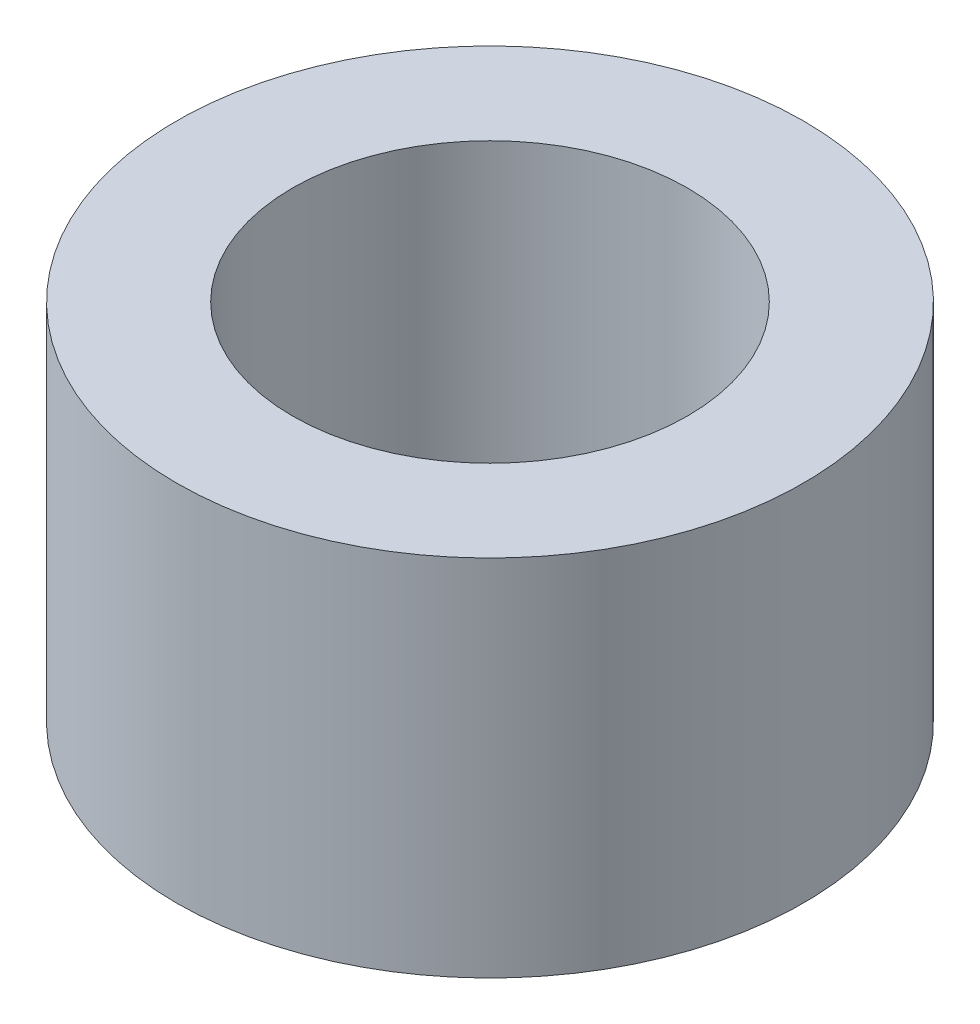
SolidWorks part; units mm, degrees
ref_plane "Front Plane" through (0, 0, 0) normal (0, 0, 1) x (1, 0, 0)
ref_plane "Top Plane" through (0, 0, 0) normal (0, 1, 0) x (1, 0, 0)
ref_plane "Right Plane" through (0, 0, 0) normal (1, 0, 0) x (0, 0, -1)
sketch "Sketch1" plane through (0, 0, 0) normal (0, 1, 0) x (1, 0, 0)
  circle A0 centre (0, 0) radius 6.35
  dimension "D1" = 12.7
extrude "Boss-Extrude1" add sketch "Sketch1" along normal blind 7.366
sketch "Sketch2" plane through (0, 7.366, 0) normal (0, 1, 0) x (1, 0, 0)
  circle A0 centre (0, 0) radius 4
  dimension "D1" = 8
sketch "Sketch3" plane through (0, 7.366, 0) normal (0, 1, 0) x (1, 0, 0)
  circle A0 centre (0, 0) radius 4
  dimension "D1" = 8
extrude "Cut-Extrude2" cut sketch "Sketch3" against normal through all
